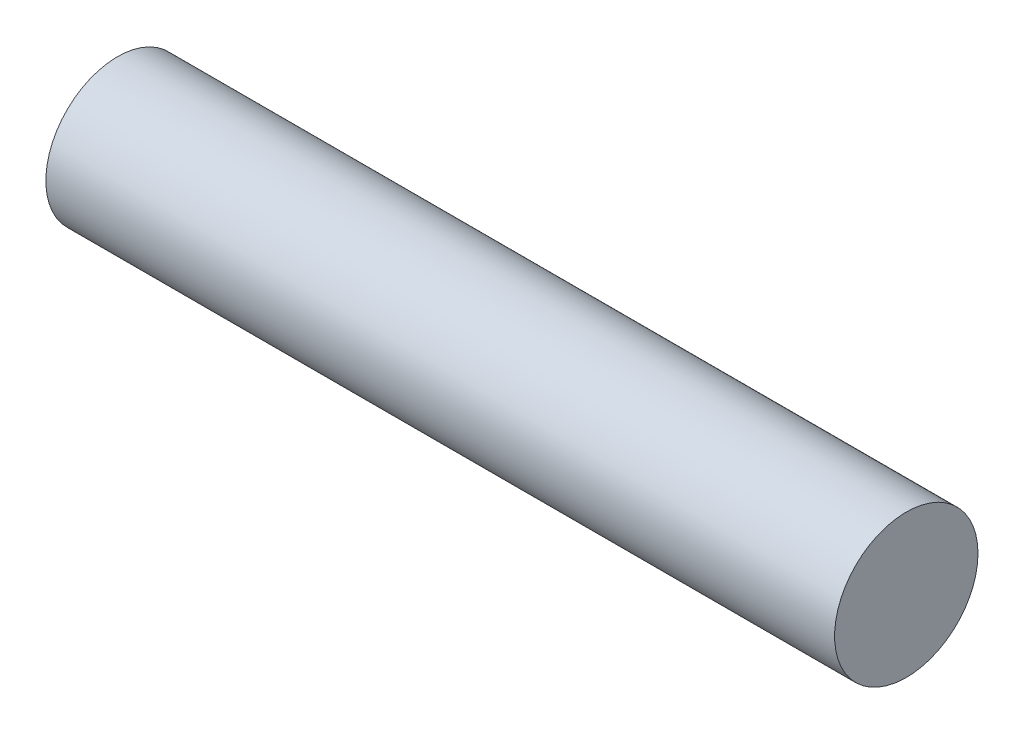
SolidWorks part; units mm, degrees
ref_plane "Front Plane" through (0, 0, 0) normal (0, 0, 1) x (1, 0, 0)
ref_plane "Top Plane" through (0, 0, 0) normal (0, 1, 0) x (1, 0, 0)
ref_plane "Right Plane" through (0, 0, 0) normal (1, 0, 0) x (0, 0, -1)
sketch "Sketch2" plane through (0, 0, 0) normal (1, 0, 0) x (0, 0, -1)
  circle A0 centre (0, 0) radius 1
  dimension "D1" = 2
extrude "Boss-Extrude1" add sketch "Sketch2" along normal blind 11
